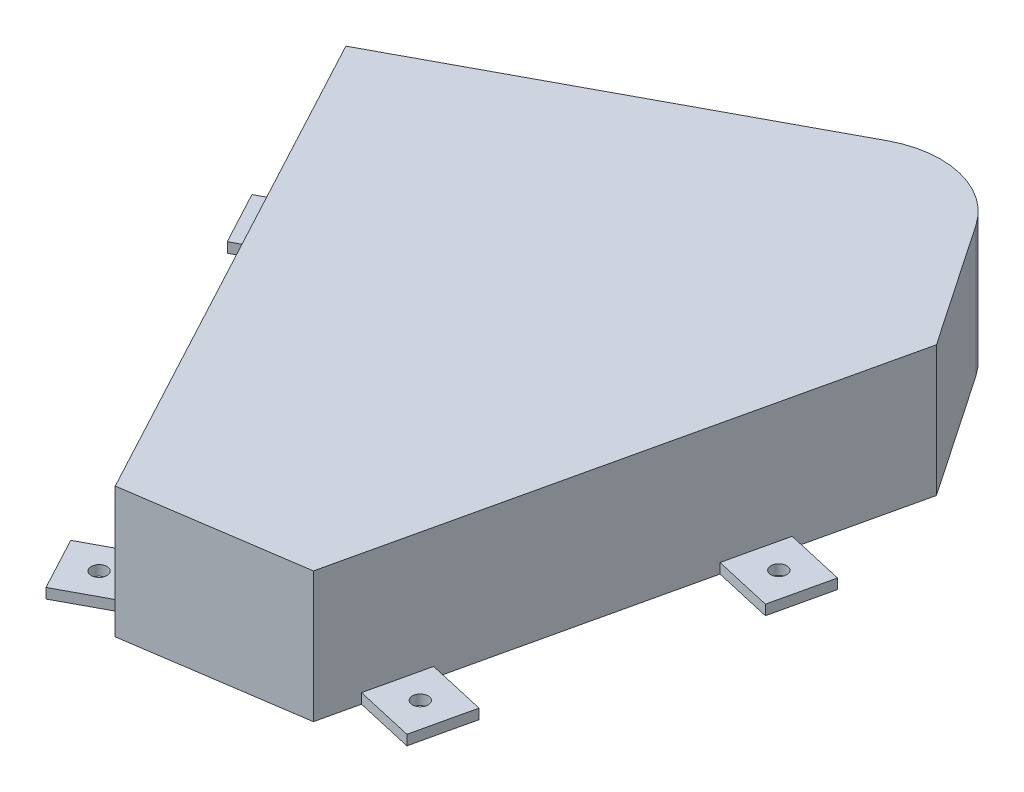
SolidWorks part; units mm, degrees
ref_plane "Front Plane" through (0, 0, 0) normal (0, 0, 1) x (1, 0, 0)
ref_plane "Top Plane" through (0, 0, 0) normal (0, 1, 0) x (1, 0, 0)
ref_plane "Right Plane" through (0, 0, 0) normal (1, 0, 0) x (0, 0, -1)
sketch "Sketch1" plane through (0, 0, 0) normal (0, 1, 0) x (1, 0, 0)
  line L0 (108.6945, 58.1876) -> (0, 0)
  line L3 (131.6337, -144.6761) -> (167.3968, 12.2534)
  line L4 (167.3968, 12.2534) -> (141.6887, 50.0735)
  line L6 (81.4356, -152.1218) -> (0, 0)
  line L7 (81.4356, -152.1218) -> (131.6337, -144.6761)
  arc A0 (141.6887, 50.0735) -> (108.6945, 58.1876) centre (120.6823, 35.7944) ccw
  point P3 (35.8898, -81.442)
  point P7 (0, 0)
  point P8 (0, 0)
  point P11 (0, 0)
  point P12 (0, 0)
  point P13 (149.8896, -134.6847)
  point P14 (131.6337, -144.6761)
  dimension "D5" = 172.548
  dimension "D6" = 90
extrude "Boss-Extrude1" add sketch "Sketch1" along normal blind 2.54
sketch "Sketch2" plane through (0, 2.54, 0) normal (0, 1, 0) x (1, 0, 0)
  line L11 (81.4356, -152.1218) -> (0, 0)
  line L12 (0, 0) -> (108.6945, 58.1876)
  line L13 (141.6887, 50.0735) -> (167.3968, 12.2534)
  line L14 (167.3968, 12.2534) -> (131.6337, -144.6761)
  line L16 (79.6911, -155.5903) -> (-4.2976, 1.3007)
  line L17 (-4.2976, 1.3007) -> (107.196, 60.9867)
  line L18 (144.3145, 51.8584) -> (170.7995, 12.8953)
  line L19 (170.7995, 12.8953) -> (134.2469, -147.4982)
  line L20 (131.6337, -144.6761) -> (81.4356, -152.1218) construction
  line L21 (134.2469, -147.4982) -> (79.6911, -155.5903) construction
  line L24 (81.4356, -152.1218) -> (131.6337, -144.6761)
  line L25 (134.2469, -147.4982) -> (79.6911, -155.5903)
  arc A0 (108.6945, 58.1876) -> (141.6887, 50.0735) centre (120.6823, 35.7944) cw
  arc A1 (107.196, 60.9867) -> (144.3145, 51.8584) centre (120.6823, 35.7944) cw
  point P14 (36.5671, -81.9955)
  dimension "D1" = 3.175
extrude "Boss-Extrude5" add sketch "Sketch2" against normal blind 41.275
sketch "Sketch6" plane through (159.5733, 0, 36.3657) normal (0.975, 0, 0.2222) x (0.2222, 0, -0.975)
  line L0 (-113.9819, -38.735) -> (50.524, -38.735) construction
  line L1 (-6.626, -38.735) -> (12.424, -38.735)
  line L2 (-6.626, -38.735) -> (-6.626, -35.56)
  line L3 (-6.626, -35.56) -> (12.424, -35.56)
  line L4 (12.424, -38.735) -> (12.424, -35.56)
  line L5 (50.524, -38.735) -> (50.524, 2.54) construction
  line L6 (-82.2319, -38.735) -> (-101.2819, -38.735)
  line L7 (-82.2319, -38.735) -> (-82.2319, -35.56)
  line L8 (-82.2319, -35.56) -> (-101.2819, -35.56)
  line L9 (-101.2819, -38.735) -> (-101.2819, -35.56)
  line L10 (-113.9819, -38.735) -> (-113.9819, 2.54) construction
  dimension "D1" = 3.175
  dimension "D2" = 38.1
  dimension "D3" = 19.05
  dimension "D4" = 19.05
  dimension "D5" = 3.175
  dimension "D6" = 12.7
extrude "Boss-Extrude6" add sketch "Sketch6" along normal blind 19.05
sketch "Sketch7" plane through (-2.7991, 0, 1.4985) normal (-0.8816, 0, 0.472) x (0.472, 0, 0.8816)
  line L0 (-3.175, -38.735) -> (174.7825, -38.735) construction
  line L1 (6.35, -38.735) -> (25.4, -38.735)
  line L2 (6.35, -38.735) -> (6.35, -35.56)
  line L3 (6.35, -35.56) -> (25.4, -35.56)
  line L4 (25.4, -38.735) -> (25.4, -35.56)
  line L5 (-3.175, -38.735) -> (-3.175, 2.54) construction
  line L6 (165.2575, -38.735) -> (146.2075, -38.735)
  line L7 (165.2575, -38.735) -> (165.2575, -35.56)
  line L8 (165.2575, -35.56) -> (146.2075, -35.56)
  line L9 (146.2075, -38.735) -> (146.2075, -35.56)
  line L10 (174.7825, -38.735) -> (174.7825, 2.54) construction
  dimension "D1" = 19.05
  dimension "D2" = 19.05
  dimension "D3" = 3.175
  dimension "D4" = 3.175
  dimension "D5" = 9.525
  dimension "D6" = 9.525
extrude "Boss-Extrude7" add sketch "Sketch7" along normal blind 19.05
sketch "Sketch8" plane through (0, -35.56, 0) normal (0, 1, 0) x (1, 0, 0)
  line L0 (-8.1996, -11.5922) -> (0.7912, -28.387) construction
  line L1 (-16.5971, -16.0876) -> (0.1978, -7.0968) construction
  line L2 (-7.6062, -32.8825) -> (9.1886, -23.8916) construction
  line L4 (49.41, -139.3888) -> (66.2049, -130.398) construction
  line L5 (57.8074, -134.8934) -> (66.7982, -151.6883) construction
  line L6 (58.4008, -156.1837) -> (75.1957, -147.1929) construction
  line L8 (155.6426, -139.3485) -> (137.0688, -135.1157) construction
  line L9 (146.3557, -137.2321) -> (150.5885, -118.6583) construction
  line L10 (159.8754, -120.7747) -> (141.3016, -116.5419) construction
  line L12 (176.6748, -47.0589) -> (158.101, -42.8261) construction
  line L13 (167.3879, -44.9425) -> (171.6207, -26.3687) construction
  line L14 (180.9076, -28.4851) -> (162.3338, -24.2523) construction
  circle A0 centre (-3.7042, -19.9896) radius 2.4892
  circle A1 centre (62.3028, -143.2909) radius 2.4892
  circle A2 centre (148.4721, -127.9452) radius 2.4892
  circle A3 centre (169.5043, -35.6556) radius 2.4892
  dimension "D1" = 4.9784
extrude "Cut-Extrude2" cut sketch "Sketch8" against normal up to next
